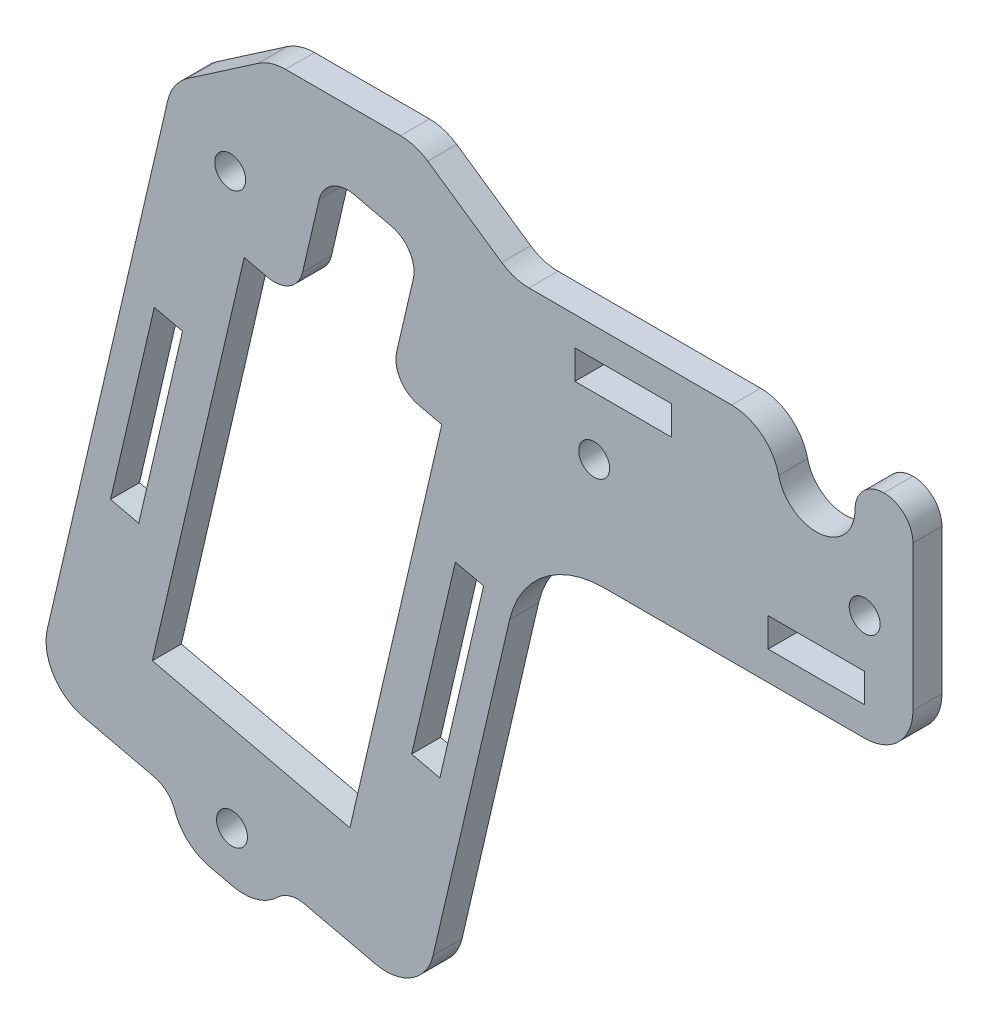
SolidWorks part; units mm, degrees
material "MDF"
ref_plane "Plano frontal" through (0, 0, 0) normal (0, 0, 1) x (1, 0, 0)
ref_plane "Plano superior" through (0, 0, 0) normal (0, 1, 0) x (1, 0, 0)
ref_plane "Plano direito" through (0, 0, 0) normal (1, 0, 0) x (0, 0, -1)
sketch "Esboço1" plane through (0, 0, 0) normal (0, 0, 1) x (1, 0, 0)
  line L0 (0, 20) -> (0, 0) construction
  line L5 (10, 16) -> (13, 16) construction
  line L6 (13, 6) -> (13, 16) construction
  line L15 (5, 11) -> (-10, 11) construction
  line L16 (10, 6) -> (13, 6) construction
  line L21 (-10, 6) -> (-13, 6) construction
  line L22 (-10, 6) -> (-10, 16) construction
  line L27 (-10, 16) -> (-13, 16) construction
  line L28 (-13, 6) -> (-13, 16) construction
  line L29 (-10, 6) -> (-13, 16) construction
  line L30 (-10, 16) -> (-13, 6) construction
  line L35 (10, 6) -> (10, 16) construction
  line L36 (18, 0) -> (18, 23)
  line L37 (18, 23) -> (-66.701, 23)
  line L43 (-29.9553, 0) -> (18, 0)
  line L61 (-68.7379, -29.9136) -> (-59.2257, 10.995)
  line L66 (-59.2257, 10.995) -> (-38.7714, 6.2389)
  line L67 (-38.7714, 6.2389) -> (-48.2836, -34.6697)
  line L68 (-48.2836, -34.6697) -> (-68.7379, -29.9136)
  line L69 (-63.9818, -9.4593) -> (-43.5275, -14.2154) construction
  line L74 (-48.9985, 8.617) -> (-58.5107, -32.2917) construction
  line L75 (-61.7051, 0.3321) -> (-41.2508, -4.424) construction
  line L80 (-38.7714, 6.2389) -> (-38.7714, -27.2218) construction
  line L85 (0, 20) -> (-15.8727, -48.263) construction
  line L86 (5, 3) -> (-5, 3)
  line L87 (-66.701, 23) -> (-80.7429, -37.389)
  line L88 (-80.7429, -37.389) -> (-40.8082, -46.6747)
  line L89 (-40.8082, -46.6747) -> (-29.9553, 0)
  line L93 (-65.6456, -40.8994) -> (-66.4949, -44.552)
  line L94 (-66.4949, -44.552) -> (-56.7548, -46.8168)
  line L95 (-55.9055, -43.1642) -> (-56.7548, -46.8168)
  line L96 (-47.0168, 17.1396) -> (-48.1492, 12.2695) construction
  line L97 (-48.1492, 12.2695) -> (-53.0193, 13.4019) construction
  line L98 (5, 3) -> (5, 6)
  line L99 (5, 6) -> (-5, 6)
  line L100 (-5, 3) -> (-5, 6)
  line L101 (0, 6) -> (0, 0) construction
  line L102 (5, 4.5) -> (-5, 4.5) construction
  line L103 (10, 0) -> (10, 23)
  line L104 (-73.0647, -17.6141) -> (-70.1427, -18.2935)
  line L105 (-70.1427, -18.2935) -> (-65.6131, 1.1868)
  line L106 (-65.6131, 1.1868) -> (-68.5351, 1.8662)
  line L107 (-38.9742, -25.5409) -> (-41.8962, -24.8615)
  line L108 (-37.3666, -5.3812) -> (-34.4446, -6.0606)
  line L109 (-41.8962, -24.8615) -> (-37.3666, -5.3812)
  line L115 (-53.8686, 9.7494) -> (-50.7875, 23)
  line L116 (-50.7875, 23) -> (-41.0474, 20.7352)
  line L117 (-25, 17) -> (-15, 17)
  line L118 (-25, 17) -> (-25, 20)
  line L119 (-25, 20) -> (-15, 20)
  line L120 (-15, 17) -> (-15, 20)
  line L121 (-20, 20) -> (-20, 17) construction
  line L122 (-25, 18.5) -> (-15, 18.5) construction
  line L123 (-68.5351, 1.8662) -> (-73.0647, -17.6141)
  line L124 (-38.9742, -25.5409) -> (-34.4446, -6.0606)
  line L125 (-41.0474, 20.7352) -> (-44.1285, 7.4846)
  line L126 (-66.701, 23) -> (-56.4985, 30)
  line L127 (-56.4985, 30) -> (-41.4985, 30)
  line L128 (-41.4985, 30) -> (-31.296, 23)
  circle A0 centre (0, 20) radius 7.5 construction
  circle A1 centre (5, 11) radius 1.6
  circle A2 centre (-10, 11) radius 1.6 construction
  circle A8 centre (-64.2301, -34.8118) radius 1.6 construction
  circle A9 centre (-54.49, -37.0766) radius 1.6 construction
  circle A10 centre (-43.2792, 11.1371) radius 1.6 construction
  circle A11 centre (-53.0193, 13.4019) radius 1.6 construction
  circle A12 centre (-47.0168, 17.1396) radius 1.6 construction
  circle A15 centre (-60.4925, -40.8143) radius 1.6
  circle A16 centre (-23, 11) radius 1.6
  circle A17 centre (-60.6769, 18) radius 1.6
  circle A18 centre (0, 20) radius 4
  point P0 (0, 20)
  point P13 (-11.5, 11)
  point P39 (-51.4779, -2.046)
  point P49 (0, 4.5)
  point P56 (-67.8779, -8.5534)
  point P61 (0, 11)
  point P72 (-20, 18.5)
  point P82 (-45.9175, 21.8676)
  point P85 (-48.9985, 30)
  dimension "D1" = 15
  dimension "D3" = 3.2
  dimension "D11" = 14.6974
  dimension "D12" = 56
  dimension "D9" = 49.5
  dimension "D30" = 5
  dimension "D31" = 5
  dimension "D28" = 10
  dimension "D35" = 7
  dimension "D36" = 5
  dimension "D25" = 8
  dimension "D2" = 15
  dimension "D4" = 5
  dimension "D5" = 21
  dimension "D6" = 10
  dimension "D7" = 3
  dimension "D8" = 42
  dimension "D10" = 10
  dimension "D13" = 20
  dimension "D14" = 5
  dimension "D15" = 10
  dimension "D16" = 10
  dimension "D17" = 6
  dimension "D18" = 5
  dimension "D19" = 7
  dimension "D20" = 5
  dimension "D21" = 13.09
  dimension "D22" = 10
  dimension "D23" = 10
  dimension "D24" = 10
  dimension "D26" = 3
  dimension "D27" = 20
  dimension "D29" = 10
  dimension "D32" = 7
  dimension "D33" = 5
  dimension "D34" = 4
  dimension "D37" = 15
  dimension "D38" = 3
  dimension "D39" = 3
extrude "Ressalto-extrusão1" add sketch "Esboço1" along normal blind 3 contours L6 A0 | L88 A15 L89 L107 L109 L108 L43 L37 L87 L106 L105 L104 A16 A12 A1 L67 L68 L61 L66 L21 L28 L27 L22 L86 L100 L99 L98 | L88 A15 L93 L94 L95 | L128 L127 L126 L37 region at (-38.7159, -3.6281, 0) region at (-61.2053, -43.8799, 0) region at (-48.9985, 26.0277, 0)
fillet "Filete1" radius 5 3 edges at (-40.8082, -46.6747, 1.5) (-80.7429, -37.389, 1.5) (10, 0, 1.5)
fillet "Filete3" radius 3 8 edges at (-65.6456, -40.8994, 1.5) (-55.9055, -43.1642, 1.5) (2.6458, 23, 1.5) (10, 23, 1.5) (-50.7875, 23, 1.5) (-41.0474, 20.7352, 1.5) (-44.1285, 7.4846, 1.5) (-53.8686, 9.7494, 1.5)
fillet "Filete4" radius 10 1 edges at (-29.9553, 0, 1.5)
fillet "Filete2" radius 5 7 edges at (-2.6458, 23, 1.5) (-56.7548, -46.8168, 1.5) (-66.4949, -44.552, 1.5) (-31.296, 23, 1.5) (-41.4985, 30, 1.5) (-56.4985, 30, 1.5) (-66.701, 23, 1.5)
